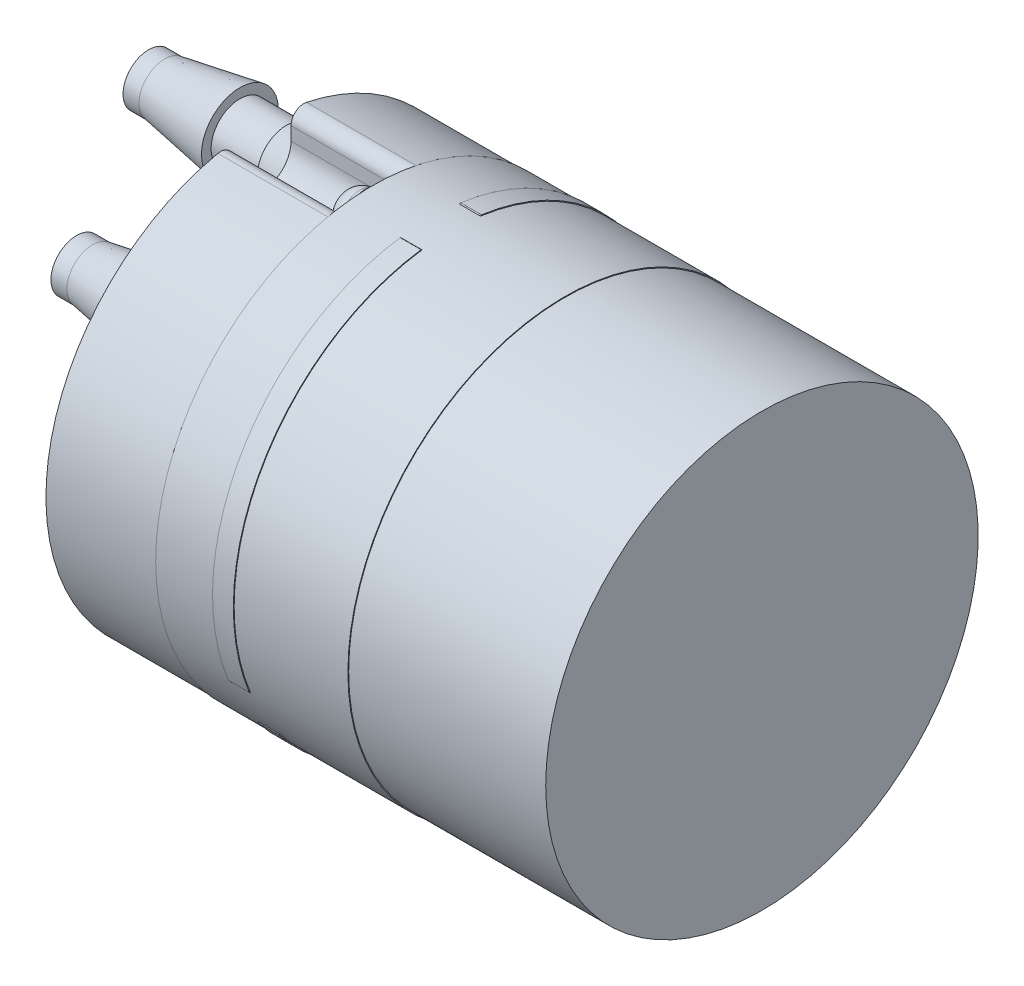
SolidWorks part; units mm, degrees
ref_plane "Front Plane" through (0, 0, 0) normal (0, 0, 1) x (1, 0, 0)
ref_plane "Top Plane" through (0, 0, 0) normal (0, 1, 0) x (1, 0, 0)
ref_plane "Right Plane" through (0, 0, 0) normal (1, 0, 0) x (0, 0, -1)
ref_plane "Base of Pump Plane" through (-31, 0, 0) normal (-1, 0, 0) x (0, 0, 1)
sketch "Pump OD Sketch" plane through (-31, 0, 0) normal (-1, 0, 0) x (0, 0, 1)
  circle A0 centre (0, 0) radius 13.5
  dimension "D1" = 27
extrude "Pump OD Extrude" add sketch "Pump OD Sketch" along normal blind 31.2 separate body
sketch "Pump Middle Sketch" plane through (-31, 0, 0) normal (-1, 0, 0) x (0, 0, 1)
  circle A0 centre (0, 0) radius 13.55
  circle A1 centre (0, 0) radius 13.5 construction
  dimension "D1" = 0.05
extrude "Pump Middle Extrude" add sketch "Pump Middle Sketch" along normal blind 12 from offset 12.3
sketch "Diaphragm Sketch" plane through (-55.3, 0, 0) normal (-1, 0, 0) x (0, 0, 1)
  line L0 (0, 0) -> (0, 12.2918) construction
  line L1 (-1.825, 12.2918) -> (1.825, 12.2918)
  line L2 (1.825, 12.2918) -> (1.825, 13.4081)
  line L3 (12.5243, -5.1236) -> (11.5575, -4.5654)
  line L4 (-1.825, 13.4081) -> (-1.825, 12.2918)
  line L5 (11.5575, -4.5654) -> (9.7325, -7.7264)
  line L6 (9.7325, -7.7264) -> (10.6993, -8.2846)
  line L7 (-10.6993, -8.2846) -> (-9.7325, -7.7264)
  line L8 (-9.7325, -7.7264) -> (-11.5575, -4.5654)
  line L9 (-11.5575, -4.5654) -> (-12.5243, -5.1236)
  arc A0 (-1.8934, 13.4676) -> (-12.6099, -5.0941) centre (0, 0) ccw
  circle A1 centre (0, 0) radius 13.55 construction
  arc A2 (1.825, 13.4081) -> (1.8934, 13.4676) centre (1.885, 13.4081) cw
  arc A3 (-1.8934, 13.4676) -> (-1.825, 13.4081) centre (-1.885, 13.4081) cw
  arc A4 (12.6099, -5.0941) -> (12.5243, -5.1236) centre (12.5543, -5.0716) cw
  arc A5 (10.6993, -8.2846) -> (10.7166, -8.3735) centre (10.6693, -8.3365) cw
  arc A6 (-10.7166, -8.3735) -> (-10.6993, -8.2846) centre (-10.6693, -8.3365) cw
  arc A7 (-12.5243, -5.1236) -> (-12.6099, -5.0941) centre (-12.5543, -5.0716) cw
  arc A8 (-10.7166, -8.3735) -> (10.7166, -8.3735) centre (0, 0) ccw
  arc A9 (12.6099, -5.0941) -> (1.8934, 13.4676) centre (0, 0) ccw
  point P32 (0, 0)
  dimension "D1" = 0.05
  dimension "D3" = 0.06
  dimension "D2" = 3.65
  dimension "D4" = 3
extrude "Diaphragm Extrude" add sketch "Diaphragm Sketch" against normal blind 1.3 from offset 3.6 offset against normal yes
sketch "Screw Pocket Sketch" plane through (-62.2, 0, 0) normal (-1, 0, 0) x (0, 0, 1)
  line L0 (0, 0) -> (0, 11.6) construction
  line L1 (-1.8, 11.6) -> (-1.8, 15.5376)
  line L2 (-1.8, 15.5376) -> (1.8, 15.5376)
  line L3 (1.8, 15.5376) -> (1.8, 11.6)
  arc A0 (-1.8, 11.6) -> (1.8, 11.6) centre (0, 11.6) ccw
  point P20 (0, 0)
  dimension "D1" = 3.6
  dimension "D2" = 11.6
extrude "Screw Pocket Cut" cut sketch "Screw Pocket Sketch" against normal up to surface (6.9 mm away) up to face at (-55.3, 0, 13.55)
fillet "Screw Pocket Fillet" radius 0.8 2 edges at (-58.75, 13.3795, -1.8) (-58.75, 13.3795, 1.8)
sketch "Scew Head Sketch" plane through (-55.3, 0, 0) normal (-1, 0, 0) x (0, 0, 1)
  circle A0 centre (0, 11.6) radius 1.3
  dimension "D1" = 2.6
extrude "Screw Head Extrude" add sketch "Scew Head Sketch" along normal blind 1.8
fillet "Screw Head Fillet" radius 1 1 edges at (-57.1, 11.6, 1.3)
sketch "Sketch10" plane through (-57.1, 0, 0) normal (-1, 0, 0) x (0, 0, 1)
  line L0 (0.15, 11.75) -> (0.15, 12.4)
  line L1 (-0.15, 10.8) -> (0.15, 10.8)
  line L2 (-0.15, 10.8) -> (-0.15, 11.45)
  line L3 (-0.15, 12.4) -> (0.15, 12.4)
  line L4 (0.15, 10.8) -> (0.15, 11.45)
  line L7 (-0.8, 11.75) -> (-0.15, 11.75)
  line L8 (-0.8, 11.75) -> (-0.8, 11.45)
  line L9 (-0.8, 11.45) -> (-0.15, 11.45)
  line L10 (0.8, 11.75) -> (0.8, 11.45)
  line L13 (0.15, 11.75) -> (0.8, 11.75)
  line L16 (0.15, 11.45) -> (0.8, 11.45)
  line L17 (-0.15, 11.75) -> (-0.15, 12.4)
  point P0 (0, 11.6)
  point P6 (0, 11.6)
  dimension "D1" = 0.3
  dimension "D2" = 1.6
extrude "Screw Drive Cut" cut sketch "Sketch10" against normal blind 1
sketch "Washer Sketch" plane through (-55.3, 0, 0) normal (-1, 0, 0) x (0, 0, 1)
  circle A0 centre (0, 11.6) radius 1.5818
extrude "Washer Extrude" add sketch "Washer Sketch" along normal blind 0.4
sketch "Center Nozzle Sketch" plane through (0, 0, 0) normal (0, 0, 1) x (1, 0, 0)
  line L0 (0, 0) -> (-76.9561, 0) construction
  line L1 (-73.7897, 1.6) -> (-72.7897, 1.6)
  line L2 (-62.2, 13.2141) -> (-62.2, -13.5) construction
  line L3 (-62.2, 2.7) -> (-65.2, 1.8)
  line L4 (-65.2, 1.8) -> (-68.0897, 1.8)
  line L5 (-68.0897, 1.8) -> (-68.0897, 2.4)
  line L6 (-72.7897, 1.6) -> (-68.0897, 2.4)
  line L7 (-73.7897, 1.6) -> (-73.7897, 1)
  line L8 (-73.7897, 1) -> (-62.2, 1)
  line L9 (-62.2, 1) -> (-62.2, 2.7)
  dimension "D1" = 3
  dimension "D2" = 5.7
  dimension "D3" = 1
  dimension "D4" = 5.4
  dimension "D5" = 3.6
  dimension "D6" = 4.8
  dimension "D7" = 3.2
  dimension "D8" = 2
  dimension "D9" = 2.8897
revolve "Center Nozzle Revolve" add sketch "Center Nozzle Sketch" angle 360 about L0
sketch "Nozzle Pattern Location Sketch" plane through (-62.2, 0, 0) normal (-1, 0, 0) x (0, 0, 1)
  line L0 (0, 0) -> (-4.5, 7.7942) construction
  line L1 (0, 0) -> (0, 4.3885) construction
  dimension "D1" = 30
  dimension "D2" = 9
pattern_linear "Nozzle LPattern" count 2 spacing 9 along (0, 0.866, -0.5) of "Center Nozzle Revolve"
